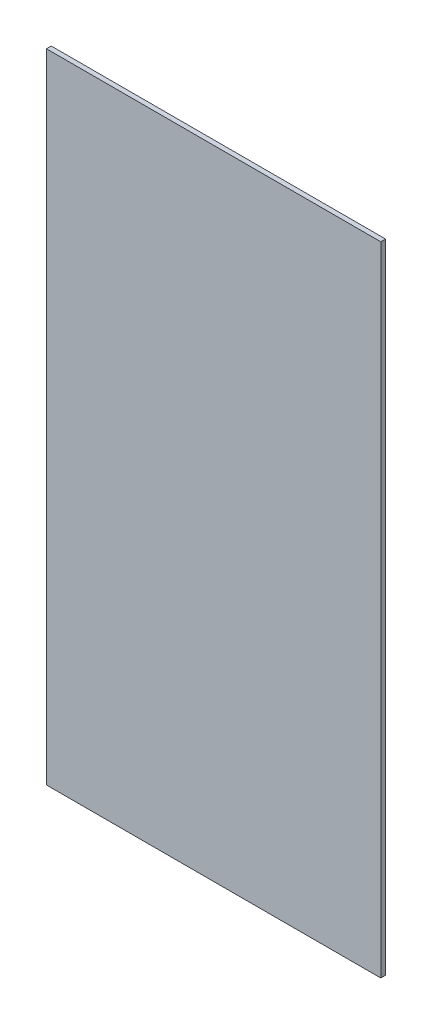
SolidWorks part; units mm, degrees
ref_plane "Спереди" through (0, 0, 0) normal (0, 0, 1) x (1, 0, 0)
ref_plane "Сверху" through (0, 0, 0) normal (0, 1, 0) x (1, 0, 0)
ref_plane "Справа" through (0, 0, 0) normal (1, 0, 0) x (0, 0, -1)
sketch "Эскиз1" plane through (0, 0, 0) normal (0, 1, 0) x (1, 0, 0)
  line L1 (-144.7882, -1.3414) -> (134.7883, -1.3414)
  line L2 (-144.7882, -1.3414) -> (-144.7882, -5.3414)
  line L3 (-144.7882, -5.3414) -> (134.7883, -5.3414)
  line L4 (134.7883, -1.3414) -> (134.7883, -5.3414)
  dimension "D1" = 4
extrude "Вытянуть1" add sketch "Эскиз1" along normal up to surface (533.2137 mm away)
sketch "Эскиз2" plane through (0, 0, 1.3414) normal (0, 0, -1) x (-1, 0, 0)
  line L1 (22.981, 111.0542) -> (106.3222, 111.0542)
  line L2 (22.981, 111.0542) -> (22.981, 26.0542)
  line L3 (22.981, 26.0542) -> (106.3222, 26.0542)
  line L4 (106.3222, 111.0542) -> (106.3222, 26.0542)
  line L5 (22.981, 111.0542) -> (106.3222, 26.0542) construction
  line L6 (22.981, 26.0542) -> (106.3222, 111.0542) construction
extrude "Вырез-Вытянуть1" cut sketch "Эскиз2" against normal blind 3
sketch "Эскиз3" plane through (0, 0, 5.3414) normal (0, 0, 1) x (1, 0, 0)
  line L1 (-63.9636, 436.4018) -> (53.666, 436.4018)
  line L2 (-73.9636, 426.4018) -> (-73.9636, 148.4471)
  line L3 (-63.9636, 138.4471) -> (53.666, 138.4471)
  line L4 (63.666, 426.4018) -> (63.666, 148.4471)
  arc A0 (-73.9636, 426.4018) -> (-63.9636, 436.4018) centre (-63.9636, 426.4018) cw
  arc A1 (63.666, 426.4018) -> (53.666, 436.4018) centre (53.666, 426.4018) ccw
  arc A2 (53.666, 138.4471) -> (63.666, 148.4471) centre (53.666, 148.4471) ccw
  arc A3 (-73.9636, 148.4471) -> (-63.9636, 138.4471) centre (-63.9636, 148.4471) ccw
  dimension "D1" = 10
